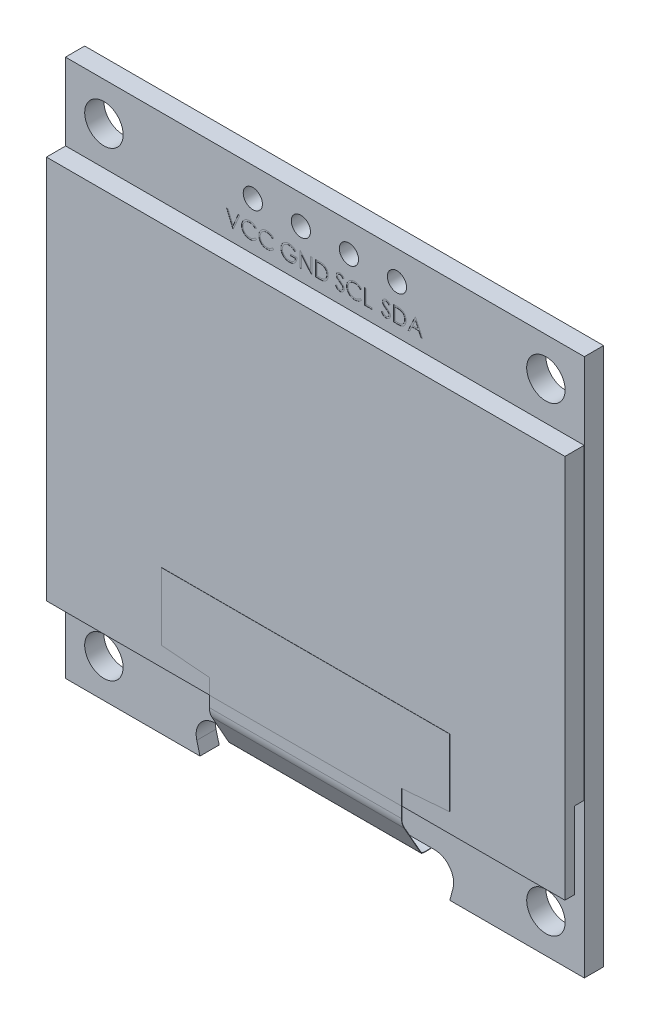
SolidWorks part; units mm, degrees
ref_plane "Alzado" through (0, 0, 0) normal (0, 0, 1) x (1, 0, 0)
ref_plane "Planta" through (0, 0, 0) normal (0, 1, 0) x (1, 0, 0)
ref_plane "Vista lateral" through (0, 0, 0) normal (1, 0, 0) x (0, 0, -1)
sketch "Croquis1" plane through (0, 0, 0) normal (0, 0, 1) x (1, 0, 0)
  line L0 (0, 0) -> (0, 13.3442) construction
  line L1 (0, 0) -> (9.7836, 0) construction
  line L2 (-13.5, 14) -> (13.5, 14)
  line L3 (-13.5, 14) -> (-13.5, -14)
  line L4 (-13.5, -14) -> (13.5, -14)
  line L5 (13.5, 14) -> (13.5, -14)
  line L6 (-13.5, 14) -> (13.5, -14) construction
  line L7 (-13.5, -14) -> (13.5, 14) construction
  circle A0 centre (11.5, 12) radius 1
  circle A1 centre (-11.5, 12) radius 1
  circle A2 centre (11.5, -12) radius 1
  circle A3 centre (-11.5, -12) radius 1
  circle A4 centre (3.75, 12.5) radius 0.5
  circle A5 centre (1.25, 12.5) radius 0.5
  circle A6 centre (-1.25, 12.5) radius 0.5
  circle A7 centre (-3.75, 12.5) radius 0.5
  dimension "D5" = 2
  dimension "D7" = 1
  dimension "D1" = 27
  dimension "D2" = 28
  dimension "D3" = 2
  dimension "D4" = 2
  dimension "D6" = 1.5
  dimension "D8" = 9.75
  dimension "D9" = 4
extrude "Saliente-Extruir1" add sketch "Croquis1" along normal blind 1
sketch "Croquis2" plane through (0, 0, 1) normal (0, 0, 1) x (1, 0, 0)
  line L0 (13.5, 14) -> (-13.5, 14) construction
  line L1 (-13.49, 10) -> (13.49, 10)
  line L2 (-13.49, 10) -> (-13.49, -6)
  line L3 (-13.49, -6) -> (13.49, -6)
  line L4 (13.49, 10) -> (13.49, -6)
  line L5 (-13.5, 14) -> (-13.5, -14) construction
  line L6 (-13.5, -14) -> (13.5, -14) construction
  line L7 (13.5, -14) -> (13.5, 14) construction
  point P0 (0, 0)
  dimension "D1" = 4
  dimension "D2" = 0.01
  dimension "D3" = 0.01
  dimension "D4" = 8
extrude "Saliente-Extruir2" add sketch "Croquis2" along normal blind 0.5 separate body
sketch "Croquis3" plane through (0, 0, 1.5) normal (0, 0, 1) x (1, 0, 0)
  line L0 (-13.49, 10) -> (-13.49, -6)
  line L2 (13.49, -6) -> (13.49, 10)
  line L3 (13.49, 10) -> (-13.49, 10)
  line L4 (-13.49, -6) -> (-13.49, -10)
  line L5 (-13.49, -10) -> (13.49, -10)
  line L6 (13.49, -10) -> (13.49, -6)
  line L7 (-13.5, -14) -> (13.5, -14) construction
  dimension "D1" = 4
extrude "Saliente-Extruir3" add sketch "Croquis3" along normal blind 0.5
sketch "Croquis4" plane through (0, 0, 2) normal (0, 0, 1) x (1, 0, 0)
  line L0 (0, -10) -> (0, 2.3423) construction
  line L1 (-13.49, -10) -> (13.49, -10) construction
  line L2 (-7.5, -5.5) -> (7.5, -5.5)
  line L3 (7.5, -5.5) -> (7.5, -9)
  line L4 (7.5, -9) -> (5, -9.2)
  line L5 (5, -9.2) -> (5, -10)
  line L6 (5, -10) -> (-5, -10)
  line L7 (-5, -9.2) -> (-5, -10)
  line L8 (-7.5, -9) -> (-5, -9.2)
  line L9 (-7.5, -5.5) -> (-7.5, -9)
  point P9 (4.5919, -9.198)
  point P15 (0, -5.5)
  dimension "D1" = 7.5
  dimension "D2" = 3.5
  dimension "D3" = 4.5
  dimension "D4" = 0.8
  dimension "D5" = 5
extrude "Saliente-Extruir4" add sketch "Croquis4" along normal blind 0.01 separate body
sketch "Croquis5" plane through (0, 0, 1) normal (0, 0, 1) x (1, 0, 0)
  line L0 (0, -14) -> (0, -10.87) construction
  line L1 (-13.5, -14) -> (13.5, -14) construction
  line L2 (-5.7001, -12.1152) -> (5.7001, -12.1152)
  line L3 (6.5, -14) -> (-6.5, -14)
  line L4 (13.5, -14) -> (13.5, 14) construction
  line L5 (-6.6667, -13.3716) -> (-6.5, -14)
  line L6 (6.6667, -13.3716) -> (6.5, -14)
  arc A0 (6.6667, -13.3716) -> (5.7001, -12.1152) centre (5.7001, -13.1152) ccw
  arc A1 (-6.6667, -13.3716) -> (-5.7001, -12.1152) centre (-5.7001, -13.1152) cw
  point P12 (7, -12.1152)
  point P17 (0, -12.1152)
  dimension "D4" = 1
  dimension "D1" = 1.95
  dimension "D2" = 7
  dimension "D3" = 6.5
extrude "Cortar-Extruir1" cut sketch "Croquis5" against normal blind 5 contours L3 L5 A1 L2 A0 L6
sketch "Croquis6" plane through (0, 0, 1) normal (0, 0, 1) x (1, 0, 0)
  line L0 (-5.159, 10.601) -> (-2.8099, 10.601) construction
  line L2 (-2.3525, 10.601) -> (0.1986, 10.601) construction
  line L4 (0.519, 10.601) -> (2.6382, 10.601) construction
  line L6 (2.9216, 10.601) -> (5.6309, 10.601) construction
  text T0 "VCC" font "Century Gothic" height in points 3
  text T1 "GND" font "Century Gothic" height in points 3
  text T2 "SCL" font "Century Gothic" height in points 3
  text T3 "SDA" font "Century Gothic" height in points 3
  point P9 (-2.1375, 10.6284)
  point P10 (-1.7717, 10.6284)
  point P11 (0, 10.7016)
  point P12 (-5.0915, 10.7199)
  point P13 (-5.3567, 10.7199)
  point P14 (0, 0)
  point P15 (-5.5762, 10.7107)
  point P16 (0.4093, 10.6793)
  point P17 (0.647, 10.6948)
  point P18 (-6.1265, 10.6497)
  point P19 (-2.466, 10.6497)
  point P20 (-2.6535, 10.6407)
  point P22 (2.6382, 10.6128)
  point P23 (3.1507, 10.6067)
  point P24 (0, 0)
  point P25 (-5.7608, 10.5913)
  point P26 (5.6309, 10.5712)
  point P27 (-5.3876, 10.5913)
  point P28 (-2.273, 10.6056)
  point P29 (2.9216, 10.6082)
  point P30 (-2.8099, 10.6149)
  point P31 (0, 0)
  point P32 (-5.159, 10.601)
  point P33 (-2.3525, 10.601)
  point P34 (0.1986, 10.601)
  point P35 (0.519, 10.601)
extrude "Cortar-Extruir2" cut sketch "Croquis6" against normal blind 0.01
sketch "Croquis7" plane through (0, 0, 0) normal (0, 0, -1) x (-1, 0, 0)
  line L0 (0, 0) -> (0, 14) construction
  line L1 (-13.5, 14) -> (13.5, 14) construction
  line L2 (13.5, 14) -> (13.5, -14) construction
  line L3 (11.5, 0.75) -> (12.5, 0.75)
  line L4 (11.5, 0.75) -> (11.5, -0.75)
  line L5 (11.5, -0.75) -> (12.5, -0.75)
  line L6 (12.5, 0.75) -> (12.5, -0.75)
  line L7 (11.5, 0.75) -> (12.5, -0.75) construction
  line L8 (11.5, -0.75) -> (12.5, 0.75) construction
  line L9 (9.5, 0.75) -> (9.5, -0.75)
  line L10 (9.5, 0.75) -> (10.5, 0.75)
  line L11 (10.5, 0.75) -> (10.5, -0.75)
  line L12 (9.5, -0.75) -> (10.5, -0.75)
  line L13 (6.375, 0.75) -> (6.375, -0.75)
  line L14 (6.375, -0.75) -> (7.375, -0.75)
  line L15 (7.375, 0.75) -> (7.375, -0.75)
  line L16 (6.375, 0.75) -> (7.375, 0.75)
  line L17 (4.875, 0.75) -> (4.875, -0.75)
  line L18 (4.875, -0.75) -> (5.875, -0.75)
  line L19 (5.875, 0.75) -> (5.875, -0.75)
  line L20 (4.875, 0.75) -> (5.875, 0.75)
  line L21 (0.875, 0.75) -> (0.875, -0.75)
  line L22 (0.875, -0.75) -> (1.875, -0.75)
  line L23 (1.875, 0.75) -> (1.875, -0.75)
  line L24 (0.875, 0.75) -> (1.875, 0.75)
  line L25 (-1.025, 0.75) -> (-1.025, -0.75)
  line L26 (-1.025, -0.75) -> (-0.025, -0.75)
  line L27 (-0.025, 0.75) -> (-0.025, -0.75)
  line L28 (-1.025, 0.75) -> (-0.025, 0.75)
  line L29 (-2.925, 0.75) -> (-2.925, -0.75)
  line L30 (-2.925, -0.75) -> (-1.925, -0.75)
  line L31 (-1.925, 0.75) -> (-1.925, -0.75)
  line L32 (-2.925, 0.75) -> (-1.925, 0.75)
  line L33 (-4.825, 0.75) -> (-4.825, -0.75)
  line L34 (-4.825, -0.75) -> (-3.825, -0.75)
  line L35 (-3.825, 0.75) -> (-3.825, -0.75)
  line L36 (-4.825, 0.75) -> (-3.825, 0.75)
  line L37 (-6.725, 0.75) -> (-6.725, -0.75)
  line L38 (-6.725, -0.75) -> (-5.725, -0.75)
  line L39 (-5.725, 0.75) -> (-5.725, -0.75)
  line L40 (-6.725, 0.75) -> (-5.725, 0.75)
  line L41 (-8.625, 0.75) -> (-8.625, -0.75)
  line L42 (-8.625, -0.75) -> (-7.625, -0.75)
  line L43 (-7.625, 0.75) -> (-7.625, -0.75)
  line L44 (-8.625, 0.75) -> (-7.625, 0.75)
  line L45 (-10.525, 0.75) -> (-10.525, -0.75)
  line L46 (-10.525, -0.75) -> (-9.525, -0.75)
  line L47 (-9.525, 0.75) -> (-9.525, -0.75)
  line L48 (-10.525, 0.75) -> (-9.525, 0.75)
  line L49 (-12.425, 0.75) -> (-12.425, -0.75)
  line L50 (-12.425, -0.75) -> (-11.425, -0.75)
  line L51 (-11.425, 0.75) -> (-11.425, -0.75)
  line L52 (-12.425, 0.75) -> (-11.425, 0.75)
  line L55 (-13.5, -14) -> (-13.5, 14) construction
  line L56 (5.6, 8.5) -> (6.6, 8.5)
  line L57 (5.6, 8.5) -> (5.6, 7)
  line L58 (5.6, 7) -> (6.6, 7)
  line L59 (6.6, 8.5) -> (6.6, 7)
  line L60 (5.6, 8.5) -> (6.6, 7) construction
  line L61 (5.6, 7) -> (6.6, 8.5) construction
  line L62 (-9, 6.6) -> (-7.5, 6.6)
  line L63 (-9, 6.6) -> (-9, 5.6)
  line L64 (-9, 5.6) -> (-7.5, 5.6)
  line L65 (-7.5, 6.6) -> (-7.5, 5.6)
  line L66 (-9, 6.6) -> (-7.5, 5.6) construction
  line L67 (-9, 5.6) -> (-7.5, 6.6) construction
  line L69 (1.1, 8) -> (3.6, 8)
  line L70 (1.1, 8) -> (1.1, 7)
  line L71 (1.1, 7) -> (3.6, 7)
  line L72 (3.6, 8) -> (3.6, 7)
  line L73 (1.1, 8) -> (3.6, 7) construction
  line L74 (1.1, 7) -> (3.6, 8) construction
  point P5 (12, 0)
  point P12 (-8.25, 6.1)
  point P58 (6.1, 7.75)
  point P68 (2.35, 7.5)
  dimension "D1" = 1
  dimension "D2" = 1.5
  dimension "D3" = 1
  dimension "D9" = 0.5
  dimension "D10" = 3
  dimension "D11" = 0.9
  dimension "D12" = 1
  dimension "D13" = 1.5
  dimension "D14" = 5.5
  dimension "D15" = 6.9
  dimension "D16" = 1.5
  dimension "D17" = 1
  dimension "D18" = 7.4
  dimension "D19" = 4.5
  dimension "D20" = 2.5
  dimension "D21" = 1
  dimension "D22" = 6
  dimension "D23" = 2
  dimension "D4" = 2
  dimension "D5" = 2
  dimension "D6" = 2
  dimension "D7" = 2
  dimension "D8" = 8
extrude "Saliente-Extruir5" add sketch "Croquis7" along normal blind 0.5 separate body
sketch "Croquis8" plane through (0, 0, -0.5) normal (0, 0, -1) x (-1, 0, 0)
  line L0 (1.1, 8) -> (3.6, 8)
  line L1 (3.6, 8) -> (1.1, 8) construction
  line L2 (3.6, 8) -> (3.6, 7)
  line L3 (1.1, 8) -> (1.1, 7)
  line L4 (1.1, 7) -> (3.6, 7) construction
  line L5 (1.1, 8) -> (1.1, 7) construction
  line L6 (1.1, 7) -> (3.6, 7)
extrude "Saliente-Extruir6" add sketch "Croquis8" along normal blind 0.5
sketch "Croquis9" plane through (0, 0, -0.5) normal (0, 0, -1) x (-1, 0, 0)
  line L0 (-8.625, 0.75) -> (-7.625, 0.75)
  line L1 (-7.625, 0.75) -> (-8.625, 0.75) construction
  line L2 (-7.625, -0.75) -> (-7.625, 0.75) construction
  line L3 (-7.625, 0.75) -> (-7.625, -0.75)
  line L4 (-7.625, -0.75) -> (-8.625, -0.75)
  line L5 (-8.625, -0.75) -> (-7.625, -0.75) construction
  line L6 (-8.625, -0.75) -> (-8.625, 0.75)
  line L7 (-8.625, 0.75) -> (-8.625, -0.75) construction
  line L8 (-6.725, -0.75) -> (-6.725, 0.75)
  line L9 (-6.725, 0.75) -> (-5.725, 0.75)
  line L10 (-5.725, 0.75) -> (-5.725, -0.75)
  line L11 (-5.725, -0.75) -> (-6.725, -0.75)
  line L12 (-4.825, -0.75) -> (-4.825, 0.75)
  line L13 (-4.825, 0.75) -> (-3.825, 0.75)
  line L14 (-3.825, 0.75) -> (-3.825, -0.75)
  line L15 (-3.825, -0.75) -> (-4.825, -0.75)
  line L16 (-2.925, -0.75) -> (-2.925, 0.75)
  line L17 (-2.925, 0.75) -> (-1.925, 0.75)
  line L18 (-1.925, 0.75) -> (-1.925, -0.75)
  line L19 (-1.925, -0.75) -> (-2.925, -0.75)
  line L20 (-9, 6.6) -> (-7.5, 6.6)
  line L21 (-9, 6.6) -> (-9, 5.6) construction
  line L22 (-7.5, 6.6) -> (-9, 6.6) construction
  line L23 (-7.5, 6.6) -> (-7.5, 5.6)
  line L24 (-7.5, 5.6) -> (-9, 5.6)
  line L25 (-9, 5.6) -> (-9, 6.6)
  point P33 (0, 0)
  dimension "D1" = 4
extrude "Cortar-Extruir4" cut sketch "Croquis9" against normal blind 0.25
sketch "Croquis10" plane through (0, 0, -0.5) normal (0, 0, -1) x (-1, 0, 0)
  line L0 (-1.025, 0.75) -> (-0.025, 0.75)
  line L1 (-0.025, 0.75) -> (-1.025, 0.75) construction
  line L2 (-1.025, 0.75) -> (-1.025, -0.75) construction
  line L3 (-0.025, 0.75) -> (-0.025, -0.75)
  line L4 (-0.025, -0.75) -> (-1.025, -0.75)
  line L5 (-1.025, -0.75) -> (-1.025, 0.75)
extrude "Cortar-Extruir5" cut sketch "Croquis10" against normal blind 0.15
sketch "Croquis11" plane through (0, 0, 0) normal (0, 0, -1) x (-1, 0, 0)
  line L0 (10.1, -4.8) -> (10.1, -6)
  line L1 (10.1, -6) -> (10.5, -6)
  line L2 (10.5, -6) -> (10.5, -4.8)
  line L3 (10.5, -4.8) -> (10.1, -4.8)
  line L4 (13.5, 14) -> (13.5, -14) construction
  line L5 (13.5, -14) -> (6.5, -14) construction
  line L6 (0, -12.1152) -> (0, -1.963) construction
  line L7 (5.7001, -12.1152) -> (-5.7001, -12.1152) construction
  line L8 (-10.5, -6) -> (-10.5, -4.8)
  line L9 (-10.1, -6) -> (-10.5, -6)
  line L10 (-10.1, -4.8) -> (-10.1, -6)
  line L11 (-10.5, -4.8) -> (-10.1, -4.8)
  line L12 (9.79, -4.8) -> (9.39, -4.8)
  line L13 (9.39, -4.8) -> (9.39, -6)
  line L14 (9.39, -6) -> (9.79, -6)
  line L15 (9.79, -6) -> (9.79, -4.8)
  line L16 (9.08, -4.8) -> (8.68, -4.8)
  line L17 (8.68, -4.8) -> (8.68, -6)
  line L18 (8.68, -6) -> (9.08, -6)
  line L19 (9.08, -6) -> (9.08, -4.8)
  line L20 (8.37, -4.8) -> (7.97, -4.8)
  line L21 (7.97, -4.8) -> (7.97, -6)
  line L22 (7.97, -6) -> (8.37, -6)
  line L23 (8.37, -6) -> (8.37, -4.8)
  line L24 (7.66, -4.8) -> (7.26, -4.8)
  line L25 (7.26, -4.8) -> (7.26, -6)
  line L26 (7.26, -6) -> (7.66, -6)
  line L27 (7.66, -6) -> (7.66, -4.8)
  line L28 (6.95, -4.8) -> (6.55, -4.8)
  line L29 (6.55, -4.8) -> (6.55, -6)
  line L30 (6.55, -6) -> (6.95, -6)
  line L31 (6.95, -6) -> (6.95, -4.8)
  line L32 (6.24, -4.8) -> (5.84, -4.8)
  line L33 (5.84, -4.8) -> (5.84, -6)
  line L34 (5.84, -6) -> (6.24, -6)
  line L35 (6.24, -6) -> (6.24, -4.8)
  line L36 (5.53, -4.8) -> (5.13, -4.8)
  line L37 (5.13, -4.8) -> (5.13, -6)
  line L38 (5.13, -6) -> (5.53, -6)
  line L39 (5.53, -6) -> (5.53, -4.8)
  line L40 (4.82, -4.8) -> (4.42, -4.8)
  line L41 (4.42, -4.8) -> (4.42, -6)
  line L42 (4.42, -6) -> (4.82, -6)
  line L43 (4.82, -6) -> (4.82, -4.8)
  line L44 (4.11, -4.8) -> (3.71, -4.8)
  line L45 (3.71, -4.8) -> (3.71, -6)
  line L46 (3.71, -6) -> (4.11, -6)
  line L47 (4.11, -6) -> (4.11, -4.8)
  line L48 (3.4, -4.8) -> (3, -4.8)
  line L49 (3, -4.8) -> (3, -6)
  line L50 (3, -6) -> (3.4, -6)
  line L51 (3.4, -6) -> (3.4, -4.8)
  line L52 (2.69, -4.8) -> (2.29, -4.8)
  line L53 (2.29, -4.8) -> (2.29, -6)
  line L54 (2.29, -6) -> (2.69, -6)
  line L55 (2.69, -6) -> (2.69, -4.8)
  line L56 (1.98, -4.8) -> (1.58, -4.8)
  line L57 (1.58, -4.8) -> (1.58, -6)
  line L58 (1.58, -6) -> (1.98, -6)
  line L59 (1.98, -6) -> (1.98, -4.8)
  line L60 (1.27, -4.8) -> (0.87, -4.8)
  line L61 (0.87, -4.8) -> (0.87, -6)
  line L62 (0.87, -6) -> (1.27, -6)
  line L63 (1.27, -6) -> (1.27, -4.8)
  line L64 (0.56, -4.8) -> (0.16, -4.8)
  line L65 (0.16, -4.8) -> (0.16, -6)
  line L66 (0.16, -6) -> (0.56, -6)
  line L67 (0.56, -6) -> (0.56, -4.8)
  line L68 (-0.15, -4.8) -> (-0.55, -4.8)
  line L69 (-0.55, -4.8) -> (-0.55, -6)
  line L70 (-0.55, -6) -> (-0.15, -6)
  line L71 (-0.15, -6) -> (-0.15, -4.8)
  line L72 (-0.86, -4.8) -> (-1.26, -4.8)
  line L73 (-1.26, -4.8) -> (-1.26, -6)
  line L74 (-1.26, -6) -> (-0.86, -6)
  line L75 (-0.86, -6) -> (-0.86, -4.8)
  line L76 (-1.57, -4.8) -> (-1.97, -4.8)
  line L77 (-1.97, -4.8) -> (-1.97, -6)
  line L78 (-1.97, -6) -> (-1.57, -6)
  line L79 (-1.57, -6) -> (-1.57, -4.8)
  line L80 (-2.28, -4.8) -> (-2.68, -4.8)
  line L81 (-2.68, -4.8) -> (-2.68, -6)
  line L82 (-2.68, -6) -> (-2.28, -6)
  line L83 (-2.28, -6) -> (-2.28, -4.8)
  line L84 (-2.99, -4.8) -> (-3.39, -4.8)
  line L85 (-3.39, -4.8) -> (-3.39, -6)
  line L86 (-3.39, -6) -> (-2.99, -6)
  line L87 (-2.99, -6) -> (-2.99, -4.8)
  line L88 (-3.7, -4.8) -> (-4.1, -4.8)
  line L89 (-4.1, -4.8) -> (-4.1, -6)
  line L90 (-4.1, -6) -> (-3.7, -6)
  line L91 (-3.7, -6) -> (-3.7, -4.8)
  line L92 (-4.41, -4.8) -> (-4.81, -4.8)
  line L93 (-4.81, -4.8) -> (-4.81, -6)
  line L94 (-4.81, -6) -> (-4.41, -6)
  line L95 (-4.41, -6) -> (-4.41, -4.8)
  line L96 (-5.12, -4.8) -> (-5.52, -4.8)
  line L97 (-5.52, -4.8) -> (-5.52, -6)
  line L98 (-5.52, -6) -> (-5.12, -6)
  line L99 (-5.12, -6) -> (-5.12, -4.8)
  line L100 (-5.83, -4.8) -> (-6.23, -4.8)
  line L101 (-6.23, -4.8) -> (-6.23, -6)
  line L102 (-6.23, -6) -> (-5.83, -6)
  line L103 (-5.83, -6) -> (-5.83, -4.8)
  line L104 (-6.54, -4.8) -> (-6.94, -4.8)
  line L105 (-6.94, -4.8) -> (-6.94, -6)
  line L106 (-6.94, -6) -> (-6.54, -6)
  line L107 (-6.54, -6) -> (-6.54, -4.8)
  line L108 (-7.25, -4.8) -> (-7.65, -4.8)
  line L109 (-7.65, -4.8) -> (-7.65, -6)
  line L110 (-7.65, -6) -> (-7.25, -6)
  line L111 (-7.25, -6) -> (-7.25, -4.8)
  line L112 (-7.96, -4.8) -> (-8.36, -4.8)
  line L113 (-8.36, -4.8) -> (-8.36, -6)
  line L114 (-8.36, -6) -> (-7.96, -6)
  line L115 (-7.96, -6) -> (-7.96, -4.8)
  line L116 (-8.67, -4.8) -> (-9.07, -4.8)
  line L117 (-9.07, -4.8) -> (-9.07, -6)
  line L118 (-9.07, -6) -> (-8.67, -6)
  line L119 (-8.67, -6) -> (-8.67, -4.8)
  line L120 (-9.38, -4.8) -> (-9.78, -4.8)
  line L121 (-9.78, -4.8) -> (-9.78, -6)
  line L122 (-9.78, -6) -> (-9.38, -6)
  line L123 (-9.38, -6) -> (-9.38, -4.8)
  dimension "D1" = 3
  dimension "D2" = 0.4
  dimension "D3" = 1.2
  dimension "D4" = 8
  dimension "D5" = 29
extrude "Saliente-Extruir7" add sketch "Croquis11" along normal blind 0.01
sketch "Croquis12" plane through (0, 0, 0) normal (0, 0, -1) x (-1, 0, 0)
  line L0 (-10.88, -6) -> (10.8003, -6)
  line L1 (10.8003, -6) -> (10.8003, -10)
  line L2 (10.8003, -10) -> (5.7001, -12.1152)
  line L3 (-0.0399, -6) -> (-0.0399, -11.376) construction
  line L4 (-10.88, -10) -> (-5.7799, -12.1152)
  line L5 (-10.88, -6) -> (-10.88, -10)
  line L6 (-5.7799, -12.1152) -> (5.7001, -12.1152)
  dimension "D1" = 4
extrude "Saliente-Extruir8" add sketch "Croquis12" along normal blind 0.02
sketch "Croquis13" plane through (0, 0, -0.02) normal (0, 0, -1) x (-1, 0, 0)
  line L0 (10.1, -6) -> (10.1, -7.7562)
  line L1 (10.1, -7.7562) -> (10.5, -7.7562)
  line L2 (10.5, -7.7562) -> (10.5, -6)
  line L3 (10.5, -6) -> (10.1, -6)
  line L4 (9.79, -6) -> (9.39, -6)
  line L5 (9.39, -6) -> (9.39, -7.7562)
  line L6 (9.39, -7.7562) -> (9.79, -7.7562)
  line L7 (9.79, -7.7562) -> (9.79, -6)
  line L8 (9.08, -6) -> (8.68, -6)
  line L9 (8.68, -6) -> (8.68, -7.7562)
  line L10 (8.68, -7.7562) -> (9.08, -7.7562)
  line L11 (9.08, -7.7562) -> (9.08, -6)
  line L12 (8.37, -6) -> (7.97, -6)
  line L13 (7.97, -6) -> (7.97, -7.7562)
  line L14 (7.97, -7.7562) -> (8.37, -7.7562)
  line L15 (8.37, -7.7562) -> (8.37, -6)
  line L16 (7.66, -6) -> (7.26, -6)
  line L17 (7.26, -6) -> (7.26, -7.7562)
  line L18 (7.26, -7.7562) -> (7.66, -7.7562)
  line L19 (7.66, -7.7562) -> (7.66, -6)
  line L20 (6.95, -6) -> (6.55, -6)
  line L21 (6.55, -6) -> (6.55, -7.7562)
  line L22 (6.55, -7.7562) -> (6.95, -7.7562)
  line L23 (6.95, -7.7562) -> (6.95, -6)
  line L24 (6.24, -6) -> (5.84, -6)
  line L25 (5.84, -6) -> (5.84, -7.7562)
  line L26 (5.84, -7.7562) -> (6.24, -7.7562)
  line L27 (6.24, -7.7562) -> (6.24, -6)
  line L28 (5.53, -6) -> (5.13, -6)
  line L29 (5.13, -6) -> (5.13, -7.7562)
  line L30 (5.13, -7.7562) -> (5.53, -7.7562)
  line L31 (5.53, -7.7562) -> (5.53, -6)
  line L32 (4.82, -6) -> (4.42, -6)
  line L33 (4.42, -6) -> (4.42, -7.7562)
  line L34 (4.42, -7.7562) -> (4.82, -7.7562)
  line L35 (4.82, -7.7562) -> (4.82, -6)
  line L36 (4.11, -6) -> (3.71, -6)
  line L37 (3.71, -6) -> (3.71, -7.7562)
  line L38 (3.71, -7.7562) -> (4.11, -7.7562)
  line L39 (4.11, -7.7562) -> (4.11, -6)
  line L40 (3.4, -6) -> (3, -6)
  line L41 (3, -6) -> (3, -7.7562)
  line L42 (3, -7.7562) -> (3.4, -7.7562)
  line L43 (3.4, -7.7562) -> (3.4, -6)
  line L44 (2.69, -6) -> (2.29, -6)
  line L45 (2.29, -6) -> (2.29, -7.7562)
  line L46 (2.29, -7.7562) -> (2.69, -7.7562)
  line L47 (2.69, -7.7562) -> (2.69, -6)
  line L48 (1.98, -6) -> (1.58, -6)
  line L49 (1.58, -6) -> (1.58, -7.7562)
  line L50 (1.58, -7.7562) -> (1.98, -7.7562)
  line L51 (1.98, -7.7562) -> (1.98, -6)
  line L52 (1.27, -6) -> (0.87, -6)
  line L53 (0.87, -6) -> (0.87, -7.7562)
  line L54 (0.87, -7.7562) -> (1.27, -7.7562)
  line L55 (1.27, -7.7562) -> (1.27, -6)
  line L56 (0.56, -6) -> (0.16, -6)
  line L57 (0.16, -6) -> (0.16, -7.7562)
  line L58 (0.16, -7.7562) -> (0.56, -7.7562)
  line L59 (0.56, -7.7562) -> (0.56, -6)
  line L60 (-0.15, -6) -> (-0.55, -6)
  line L61 (-0.55, -6) -> (-0.55, -7.7562)
  line L62 (-0.55, -7.7562) -> (-0.15, -7.7562)
  line L63 (-0.15, -7.7562) -> (-0.15, -6)
  line L64 (-0.86, -6) -> (-1.26, -6)
  line L65 (-1.26, -6) -> (-1.26, -7.7562)
  line L66 (-1.26, -7.7562) -> (-0.86, -7.7562)
  line L67 (-0.86, -7.7562) -> (-0.86, -6)
  line L68 (-1.57, -6) -> (-1.97, -6)
  line L69 (-1.97, -6) -> (-1.97, -7.7562)
  line L70 (-1.97, -7.7562) -> (-1.57, -7.7562)
  line L71 (-1.57, -7.7562) -> (-1.57, -6)
  line L72 (-2.28, -6) -> (-2.68, -6)
  line L73 (-2.68, -6) -> (-2.68, -7.7562)
  line L74 (-2.68, -7.7562) -> (-2.28, -7.7562)
  line L75 (-2.28, -7.7562) -> (-2.28, -6)
  line L76 (-2.99, -6) -> (-3.39, -6)
  line L77 (-3.39, -6) -> (-3.39, -7.7562)
  line L78 (-3.39, -7.7562) -> (-2.99, -7.7562)
  line L79 (-2.99, -7.7562) -> (-2.99, -6)
  line L80 (-3.7, -6) -> (-4.1, -6)
  line L81 (-4.1, -6) -> (-4.1, -7.7562)
  line L82 (-4.1, -7.7562) -> (-3.7, -7.7562)
  line L83 (-3.7, -7.7562) -> (-3.7, -6)
  line L84 (-4.41, -6) -> (-4.81, -6)
  line L85 (-4.81, -6) -> (-4.81, -7.7562)
  line L86 (-4.81, -7.7562) -> (-4.41, -7.7562)
  line L87 (-4.41, -7.7562) -> (-4.41, -6)
  line L88 (-5.12, -6) -> (-5.52, -6)
  line L89 (-5.52, -6) -> (-5.52, -7.7562)
  line L90 (-5.52, -7.7562) -> (-5.12, -7.7562)
  line L91 (-5.12, -7.7562) -> (-5.12, -6)
  line L92 (-5.83, -6) -> (-6.23, -6)
  line L93 (-6.23, -6) -> (-6.23, -7.7562)
  line L94 (-6.23, -7.7562) -> (-5.83, -7.7562)
  line L95 (-5.83, -7.7562) -> (-5.83, -6)
  line L96 (-6.54, -6) -> (-6.94, -6)
  line L97 (-6.94, -6) -> (-6.94, -7.7562)
  line L98 (-6.94, -7.7562) -> (-6.54, -7.7562)
  line L99 (-6.54, -7.7562) -> (-6.54, -6)
  line L100 (-7.25, -6) -> (-7.65, -6)
  line L101 (-7.65, -6) -> (-7.65, -7.7562)
  line L102 (-7.65, -7.7562) -> (-7.25, -7.7562)
  line L103 (-7.25, -7.7562) -> (-7.25, -6)
  line L104 (-7.96, -6) -> (-8.36, -6)
  line L105 (-8.36, -6) -> (-8.36, -7.7562)
  line L106 (-8.36, -7.7562) -> (-7.96, -7.7562)
  line L107 (-7.96, -7.7562) -> (-7.96, -6)
  line L108 (-8.67, -6) -> (-9.07, -6)
  line L109 (-9.07, -6) -> (-9.07, -7.7562)
  line L110 (-9.07, -7.7562) -> (-8.67, -7.7562)
  line L111 (-8.67, -7.7562) -> (-8.67, -6)
  line L112 (-9.38, -6) -> (-9.78, -6)
  line L113 (-9.78, -6) -> (-9.78, -7.7562)
  line L114 (-9.78, -7.7562) -> (-9.38, -7.7562)
  line L115 (-9.38, -7.7562) -> (-9.38, -6)
  line L116 (-10.09, -6) -> (-10.49, -6)
  line L117 (-10.49, -6) -> (-10.49, -7.7562)
  line L118 (-10.49, -7.7562) -> (-10.09, -7.7562)
  line L119 (-10.09, -7.7562) -> (-10.09, -6)
  dimension "D1" = 30
extrude "Saliente-Extruir9" add sketch "Croquis13" along normal blind 0.01 separate body
sketch "Croquis14" plane through (0, 0, 0) normal (1, 0, 0) x (0, 0, -1)
  line L0 (-1.8712, -11.0337) -> (-1, -12.5799)
  line L1 (-1, -14) -> (-1, 14) construction
  line L6 (-1.8812, -11.0543) -> (-1, -12.6182)
  line L7 (-1, 14) -> (-1, -14) construction
  line L8 (0, -12.1152) -> (0.02, -12.1152)
  line L9 (-2.01, -10) -> (-2.01, -10.5634)
  line L10 (-2.01, -10) -> (-2, -10)
  line L11 (-2, -10) -> (-2, -10.5428)
  arc A0 (-1.8712, -11.0337) -> (-2, -10.5428) centre (-1, -10.5428) cw
  arc A1 (-2.01, -10.5634) -> (-1.8812, -11.0543) centre (-1.01, -10.5634) ccw
  spline S0 degree 3 poles (-1, -12.5799) (-0.9623, -12.6467) (-0.711, -12.6592) (-0.3062, -12.6521) (0.037, -12.3841) (0, -12.1152) knots 0 0 0 0 0.172334 0.476531 1 1 1 1
  spline S1 degree 3 poles (-1, -12.6182) (-0.9777, -12.6578) (-0.792, -12.6818) (-0.5247, -12.6884) (-0.1125, -12.5625) (0.0554, -12.2888) (0.02, -12.1152) knots 0 0 0 0 0.100865 0.351857 0.644151 1 1 1 1
  point P4 (0, 0)
  point P5 (-1.4971, -10.8084)
  point P7 (0, 0)
  point P8 (0, 0)
  point P9 (0, 0)
  point P20 (0, 0)
extrude "Saliente-Extruir12" add sketch "Croquis14" along normal blind 5 and the other way blind 5 contours L8 S1 L6 A1 L9 L10 L11 A0 L0 S0
fillet "Redondeo1" radius 0.2 8 edges at (11.925, -0.75, -0.5) (11.925, -0.75, 0) (12.425, 0.75, -0.25) (12.425, -0.75, -0.25) (11.425, -0.75, -0.25) (11.425, 0.75, -0.25) (11.925, 0.75, -0.5) (11.925, 0.75, 0)
fillet "Redondeo2" radius 0.2 8 edges at (10.525, -0.75, -0.25) (10.025, -0.75, -0.5) (9.525, -0.75, -0.25) (10.025, -0.75, 0) (9.525, 0.75, -0.25) (10.025, 0.75, -0.5) (10.525, 0.75, -0.25) (10.025, 0.75, 0)
fillet "Redondeo3" radius 0.2 8 edges at (-11.5, -0.75, -0.25) (-12, -0.75, -0.5) (-12.5, -0.75, -0.25) (-12, -0.75, 0) (-12.5, 0.75, -0.25) (-12, 0.75, -0.5) (-11.5, 0.75, -0.25) (-12, 0.75, 0)
fillet "Redondeo4" radius 0.2 8 edges at (-9.5, -0.75, -0.25) (-10, -0.75, -0.5) (-10.5, -0.75, -0.25) (-10, -0.75, 0) (-10.5, 0.75, -0.25) (-10, 0.75, -0.5) (-9.5, 0.75, -0.25) (-10, 0.75, 0)
fillet "Redondeo5" radius 0.2 8 edges at (-6.375, -0.75, -0.25) (-6.875, -0.75, -0.5) (-7.375, -0.75, -0.25) (-6.875, -0.75, 0) (-7.375, 0.75, -0.25) (-6.875, 0.75, -0.5) (-6.375, 0.75, -0.25) (-6.875, 0.75, 0)
fillet "Redondeo6" radius 0.2 8 edges at (-4.875, -0.75, -0.25) (-5.375, -0.75, -0.5) (-5.875, -0.75, -0.25) (-5.375, -0.75, 0) (-5.875, 0.75, -0.25) (-5.375, 0.75, -0.5) (-4.875, 0.75, -0.25) (-5.375, 0.75, 0)
fillet "Redondeo7" radius 0.2 8 edges at (-0.875, -0.75, -0.25) (-1.375, -0.75, -0.5) (-1.875, -0.75, -0.25) (-1.375, -0.75, 0) (-1.875, 0.75, -0.25) (-1.375, 0.75, -0.5) (-0.875, 0.75, -0.25) (-1.375, 0.75, 0)
fillet "Redondeo8" radius 0.2 8 edges at (-6.6, 8.5, -0.25) (-6.1, 8.5, -0.5) (-5.6, 8.5, -0.25) (-6.1, 8.5, 0) (-5.6, 7, -0.25) (-6.1, 7, -0.5) (-6.6, 7, -0.25) (-6.1, 7, 0)
fillet "Redondeo9" radius 0.1 5 edges at (6.225, -0.75, 0) (6.725, -0.75, -0.125) (6.225, -0.75, -0.25) (5.725, -0.75, -0.125) (6.225, 0.75, -0.25)
fillet "Redondeo10" radius 0.1 8 edges at (4.325, 0.75, 0) (3.825, 0.75, -0.125) (4.325, 0.75, -0.25) (4.825, 0.75, -0.125) (4.325, -0.75, 0) (4.825, -0.75, -0.125) (4.325, -0.75, -0.25) (3.825, -0.75, -0.125)
fillet "Redondeo11" radius 0.1 8 edges at (2.425, -0.75, 0) (2.925, -0.75, -0.125) (2.425, -0.75, -0.25) (1.925, -0.75, -0.125) (2.425, 0.75, 0) (1.925, 0.75, -0.125) (2.425, 0.75, -0.25) (2.925, 0.75, -0.125)
fillet "Redondeo12" radius 0.1 8 edges at (8.125, 0.75, 0) (7.625, 0.75, -0.125) (8.125, 0.75, -0.25) (8.625, 0.75, -0.125) (8.125, -0.75, 0) (8.625, -0.75, -0.125) (8.125, -0.75, -0.25) (7.625, -0.75, -0.125)
fillet "Redondeo13" radius 0.1 8 edges at (7.5, 6.1, 0) (7.5, 5.6, -0.125) (7.5, 6.1, -0.25) (7.5, 6.6, -0.125) (9, 6.1, 0) (9, 6.6, -0.125) (9, 6.1, -0.25) (9, 5.6, -0.125)
